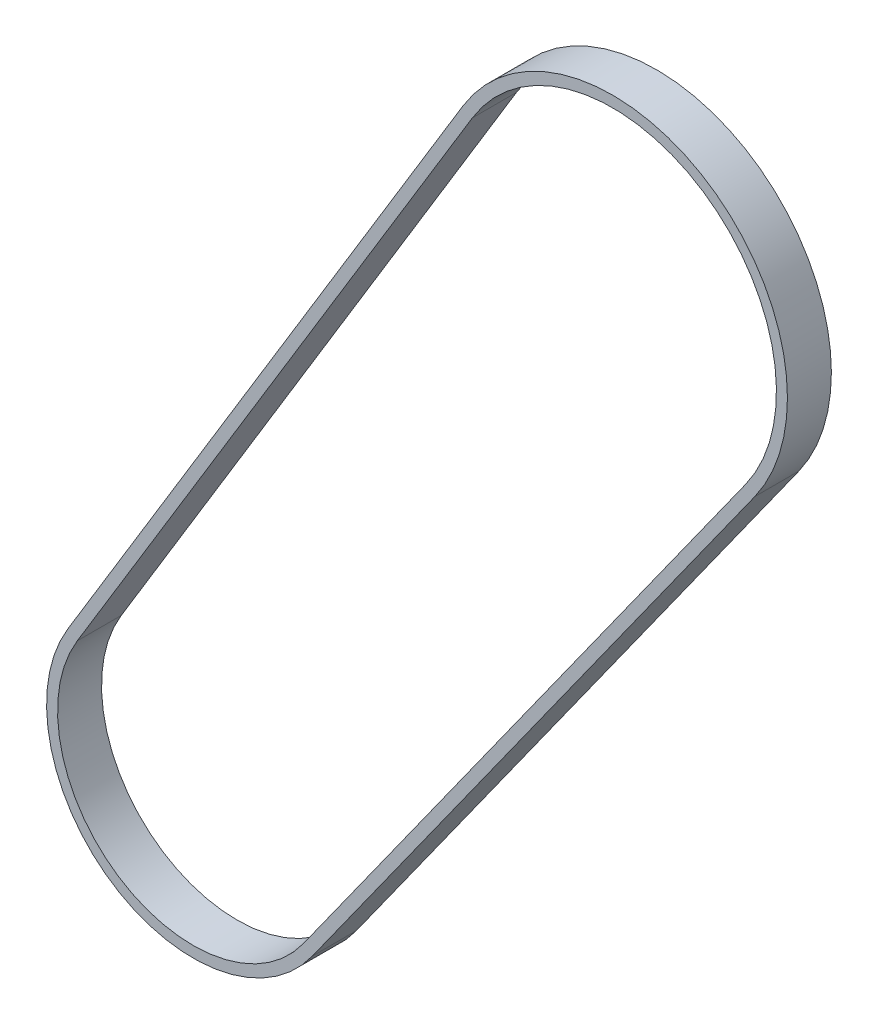
SolidWorks part; units mm, degrees
ref_plane "Front Plane" through (0, 0, 0) normal (0, 0, 1) x (1, 0, 0)
ref_plane "Top Plane" through (0, 0, 0) normal (0, 1, 0) x (1, 0, 0)
ref_plane "Right Plane" through (0, 0, 0) normal (1, 0, 0) x (0, 0, -1)
sketch "Sketch2" plane through (0, 0, 0) normal (0, 0, 1) x (1, 0, 0)
  line L0 (0, 0) -> (1, 0) construction
  line L1 (0, 0) -> (0, 1) construction
  line L6 (-17.0933, 10.3837) -> (36.8541, 99.19)
  line L7 (76.6858, 72.9122) -> (16.2722, -11.6283)
  arc A2 (36.8541, 99.19) -> (76.6858, 72.9122) centre (57.2601, 86.794) cw
  arc A4 (16.2722, -11.6283) -> (-17.0933, 10.3837) centre (0, 0) cw
extrude "Extrude-Thin1" add sketch "Sketch2" against normal blind 6 thin thin type one direction reverse wall 1.5
